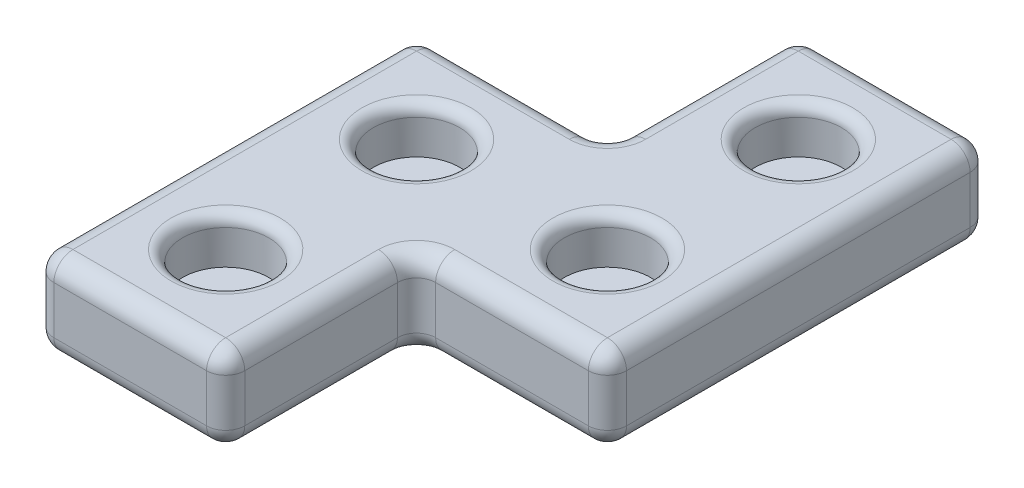
SolidWorks part; units mm, degrees
ref_plane "Front Plane" through (0, 0, 0) normal (0, 0, 1) x (1, 0, 0)
ref_plane "Top Plane" through (0, 0, 0) normal (0, 1, 0) x (1, 0, 0)
ref_plane "Right Plane" through (0, 0, 0) normal (1, 0, 0) x (0, 0, -1)
sketch "Sketch1" plane through (0, 0, 0) normal (0, 1, 0) x (1, 0, 0)
  line L0 (-7.6659, 2.6651) -> (-7.6659, 12.8251)
  line L1 (-6.3959, 14.0951) -> (3.7641, 14.0951)
  line L2 (5.0341, 12.8251) -> (5.0341, -10.0349)
  line L3 (3.7641, -11.3049) -> (-6.3959, -11.3049)
  line L4 (-7.6659, -12.5749) -> (-7.6659, -22.7349)
  line L5 (-8.9359, -24.0049) -> (-19.0959, -24.0049)
  line L6 (-20.3659, -22.7349) -> (-20.3659, 0.1251)
  line L7 (-19.0959, 1.3951) -> (-8.9359, 1.3951)
  arc A0 (-7.6659, 2.6651) -> (-8.9359, 1.3951) centre (-8.9359, 2.6651) cw
  arc A1 (-6.3959, -11.3049) -> (-7.6659, -12.5749) centre (-6.3959, -12.5749) ccw
  arc A2 (-7.6659, -22.7349) -> (-8.9359, -24.0049) centre (-8.9359, -22.7349) cw
  arc A3 (-19.0959, -24.0049) -> (-20.3659, -22.7349) centre (-19.0959, -22.7349) cw
  arc A4 (-20.3659, 0.1251) -> (-19.0959, 1.3951) centre (-19.0959, 0.1251) cw
  arc A5 (5.0341, -10.0349) -> (3.7641, -11.3049) centre (3.7641, -10.0349) cw
  arc A6 (-7.6659, 12.8251) -> (-6.3959, 14.0951) centre (-6.3959, 12.8251) cw
  arc A7 (3.7641, 14.0951) -> (5.0341, 12.8251) centre (3.7641, 12.8251) cw
  point P10 (-7.6659, 1.3951)
  point P13 (-7.6659, -11.3049)
  point P18 (-20.3659, -24.0049)
  point P21 (-20.3659, 1.3951)
  point P24 (5.0341, -11.3049)
  point P27 (-7.6659, 14.0951)
  point P30 (5.0341, 14.0951)
  dimension "D7" = 1.27
  dimension "D1" = 12.7
  dimension "D2" = 25.4
  dimension "D3" = 12.7
  dimension "D4" = 25.4
  dimension "D5" = 12.7
  dimension "D6" = 12.7
extrude "Boss-Extrude1" add sketch "Sketch1" along normal blind 5.715
sketch "Sketch2" plane through (0, 5.715, 0) normal (0, 1, 0) x (1, 0, 0)
  line L0 (5.0341, -10.0349) -> (5.0341, 12.8251) construction
  line L1 (-19.0959, -24.0049) -> (-8.9359, -24.0049) construction
  circle A0 centre (-1.3159, 7.7451) radius 2.8702
  circle A1 centre (-14.0159, -4.9549) radius 2.8702
  circle A2 centre (-14.0159, -17.6549) radius 2.8702
  circle A3 centre (-1.3159, -4.9549) radius 2.8702
  dimension "D1" = 6.35
  dimension "D2" = 12.7
  dimension "D3" = 12.7
  dimension "D4" = 12.7
  dimension "D5" = 6.35
extrude "Cut-Extrude1" cut sketch "Sketch2" against normal blind 3.048
fillet "Fillet1" radius 1.27 16 edges at (-1.3159, 5.715, 11.3049) (-7.6659, 5.715, 17.6549) (-14.0159, 5.715, 24.0049) (-20.3659, 5.715, 11.3049) (-14.0159, 5.715, -1.3951) (-7.6659, 5.715, -7.7451) (-1.3159, 5.715, -14.0951) (5.0341, 5.715, -1.3951) (4.6621, 5.715, 10.9329) (-7.2939, 5.715, 11.6769) (-8.0379, 5.715, 23.6329) (-19.9939, 5.715, 23.6329) (-19.9939, 5.715, -1.0231) (-8.0379, 5.715, -1.7671) (-7.2939, 5.715, -13.7231) (4.6621, 5.715, -13.7231)
fillet "Fillet2" radius 1.27 16 edges at (-1.3159, 0, -14.0951) (-7.6659, 0, -7.7451) (-14.0159, 0, -1.3951) (-20.3659, 0, 11.3049) (-14.0159, 0, 24.0049) (-7.6659, 0, 17.6549) (-1.3159, 0, 11.3049) (5.0341, 0, -1.3951) (4.6621, 0, 10.9329) (-7.2939, 0, 11.6769) (-8.0379, 0, 23.6329) (-19.9939, 0, 23.6329) (-19.9939, 0, -1.0231) (-8.0379, 0, -1.7671) (-7.2939, 0, -13.7231) (4.6621, 0, -13.7231)
fillet "Fillet3" radius 0.762 4 edges at (-14.0159, 5.715, 20.5251) (-14.0159, 5.715, 7.8251) (-1.3159, 5.715, 7.8251) (-1.3159, 5.715, -4.8749)
